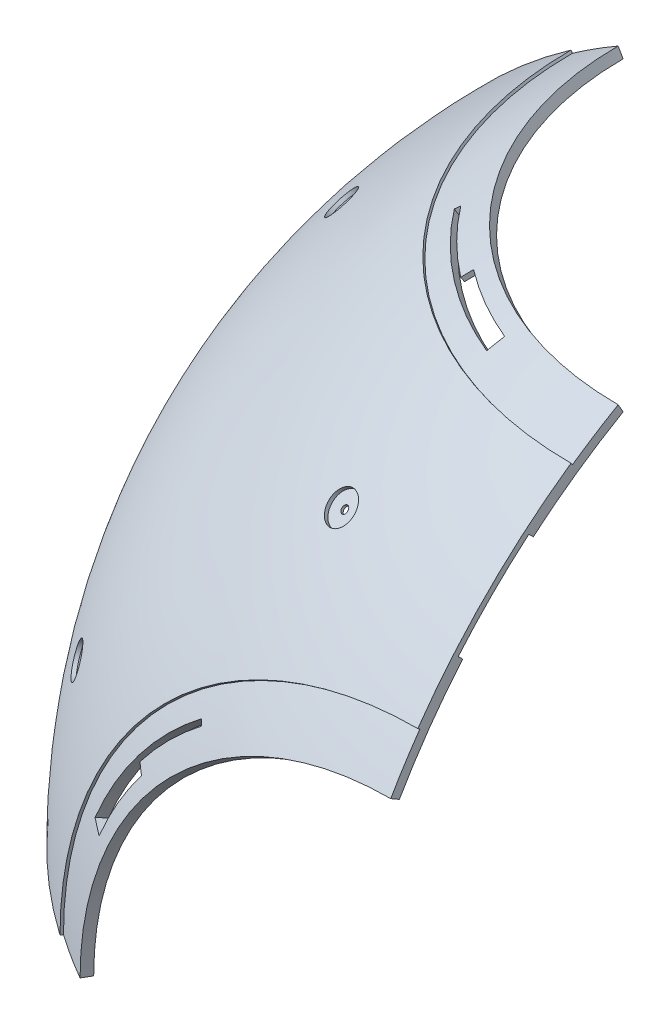
SolidWorks part; units mm, degrees
ref_plane "Front Plane" through (0, 0, 0) normal (0, 0, 1) x (1, 0, 0)
ref_plane "Top Plane" through (0, 0, 0) normal (0, 1, 0) x (1, 0, 0)
ref_plane "Right Plane" through (0, 0, 0) normal (1, 0, 0) x (0, 0, -1)
sketch "Sketch1" plane through (0, 0, 0) normal (0, 0, 1) x (1, 0, 0)
  line L0 (0, 0) -> (0, 282.4311)
  line L1 (-122.5, 212.1762) -> (-124.5, 215.6403)
  line L2 (-142.8205, 203.9689) -> (-143.3941, 204.788)
  line L3 (-245, 0) -> (-250, 0)
  arc A0 (-143.3941, 204.788) -> (-250, 0) centre (0, 0) ccw
  arc A1 (-124.5, 215.6403) -> (-142.8205, 203.9689) centre (0, 0) ccw
  arc A2 (-122.5, 212.1762) -> (-245, 0) centre (0, 0) ccw
  dimension "D1" = 500
  dimension "D2" = 498
  dimension "D3" = 490
  dimension "D4" = 5
  dimension "D5" = 30
revolve "Revolve1" add sketch "Sketch1" angle 90 about L0 region at (-214.3457, 123.7526, 0)
sketch "Sketch2" plane through (0, 0, 0) normal (1, 0, 0) x (0, 0, -1)
  line L0 (0, 0) -> (-288.7114, 0)
  line L1 (-212.1762, 122.5) -> (-215.6403, 124.5)
  line L2 (-203.9689, 142.8205) -> (-204.788, 143.3941)
  arc A0 (-204.788, 143.3941) -> (-250, 0) centre (0, 0) ccw
  arc A1 (-212.1762, 122.5) -> (-245, 0) centre (0, 0) ccw
  arc A2 (-203.9689, 142.8205) -> (-215.6403, 124.5) centre (0, 0) ccw
  dimension "D1" = 498
  dimension "D2" = 490
  dimension "D3" = 5
  dimension "D4" = 30
revolve "Cut-Revolve2" cut sketch "Sketch2" angle 360 about L0 region at (0, 1.506, 247.5)
sketch "Sketch3" plane through (0, 0, 0) normal (0, 0, -1) x (-1, 0, 0)
  line L0 (0, 0) -> (307.3195, 0)
  line L1 (203.9689, 142.8205) -> (204.788, 143.3941)
  line L2 (0, 0) -> (215.6403, 124.5)
  arc A0 (245, 0) -> (212.1762, 122.5) centre (0, 0) ccw
  arc A1 (250, 0) -> (204.788, 143.3941) centre (0, 0) ccw
  arc A2 (215.6403, 124.5) -> (203.9689, 142.8205) centre (0, 0) ccw
  dimension "D1" = 498
  dimension "D2" = 30
  dimension "D3" = 5
revolve "Cut-Revolve3" cut sketch "Sketch3" angle 360 about L0 region at (-238.1065, 63.8005, 0)
sketch "Sketch10" plane through (0, 0, 0) normal (0, 0, 1) x (1, 0, 0)
  line L0 (0, 0) -> (-235.3166, 0)
  line L1 (0, 0) -> (-214.7234, 214.7234)
  dimension "D1" = 45
ref_plane "Plane1" through (0, 0, 0) normal (0, -0.3827, 0.9239) x (-1, 0, 0)
sketch "Sketch11" plane through (0, 0, 0) normal (0, -0.3827, 0.9239) x (-1, 0, 0)
  line L0 (0, 0) -> (212.3074, -130.1021)
  line L1 (0, 0) -> (208.829, -135.6151)
  line L2 (0, 0) -> (204.788, -143.3941)
  line L3 (0, 0) -> (271.2872, 0)
  circle A0 centre (0, 0) radius 249
  circle A1 centre (0, 0) radius 245
  dimension "D1" = 498
  dimension "D2" = 490
  dimension "D3" = 1.5
  dimension "D4" = 2
revolve "Cut-Revolve4" cut sketch "Sketch11" angle 15 about L0 region at (-208.8934, 121.7691, 50.4384) reverse direction yes
sketch "Sketch12" plane through (0, 0, 0) normal (0, 0.6088, -0.7934) x (1, 0, 0)
  line L0 (0, 0) -> (-210.0045, -133.7876)
  line L1 (0, 0) -> (-208.829, -135.6151)
  line L2 (0, 0) -> (-204.788, -143.3941)
  line L3 (0, 0) -> (-212.3074, -130.1021)
  circle A0 centre (0, 0) radius 249
  circle A1 centre (0, 0) radius 245
  circle A2 centre (0, 0) radius 247
  dimension "D1" = 490
  dimension "D4" = 494
  dimension "D2" = 2
  dimension "D3" = 0.5
revolve "Cut-Revolve5" cut sketch "Sketch12" angle 15 about L0 region at (-206.8961, 105.5795, 81.014) region at (-208.6183, 103.4209, 79.3577) region at (-208.5781, 106.4378, 81.6726) reverse direction yes
ref_plane "Plane2" through (0, 0, 0) normal (0, -0.7071, 0.7071) x (-1, 0, 0)
sketch "Sketch15" plane through (0, 0, 0) normal (0, 1, 0) x (1, 0, 0)
  line L1 (0, 0) -> (-189.3752, -189.3752)
  line L2 (0, 0) -> (0, -178.2847)
  dimension "D1" = 45
ref_plane "Plane3" through (0, 0, 0) normal (-0.7071, 0, -0.7071) x (-0.7071, 0, 0.7071)
ref_axis "Axis1" through (9.4688, -9.4688, -9.4688) along (-0.5774, 0.5774, 0.5774)
pattern_circular "CirPattern5" count 3 every 120 about axis through (9.4688, -9.4688, -9.4688) along (-0.5774, 0.5774, 0.5774) of "Cut-Revolve4", "Cut-Revolve5"
sketch "Sketch18" plane through (0, 0, 0) normal (-0.7071, 0, -0.7071) x (-0.7071, 0, 0.7071)
  line L0 (0, 0) -> (0, 83.9389)
ref_plane "Plane5" through (0, 0, 0) normal (-0.7071, 0, 0.7071) x (0, 1, 0)
sketch "Sketch19" plane through (0, 0, 0) normal (-0.7071, 0, 0.7071) x (0, 1, 0)
  line L0 (0, 64.4459) -> (0, -64.4459)
sketch "Sketch20" plane through (0, 0, 0) normal (0, -1, 0) x (1, 0, 0)
  line L0 (0, 0) -> (-202.4375, 202.4375)
  line L1 (14.1421, 14.1421) -> (-188.2954, 216.5796)
  line L2 (-14.1421, -14.1421) -> (-216.5796, 188.2954)
  circle A0 centre (0, 0) radius 247.5
  circle A1 centre (0, 0) radius 245
  dimension "D3" = 495
  dimension "D1" = 20
  dimension "D2" = 20
revolve "Cut-Revolve6" cut sketch "Sketch20" angle 20 about L0 region at (-181.0082, 0, 166.8583) region at (-166.8583, 0, 181.0082) reverse direction yes
pattern_circular "CirPattern6" count 3 over 360 about axis through (9.4688, -9.4688, -9.4688) along (-0.5774, 0.5774, 0.5774) of "Cut-Revolve6"
ref_plane "Plane6" through (0, 0, 0) normal (0.183, 0.9659, -0.183) x (0.7071, 0, 0.7071)
sketch "Sketch21" plane through (0, 0, 0) normal (0.183, 0.9659, -0.183) x (0.7071, 0, 0.7071)
  line L0 (0, 0) -> (0, -320.9384)
sketch "Sketch22" plane through (0, 0, 0) normal (-0.7071, 0, -0.7071) x (-0.7071, 0, 0.7071)
  line L0 (0, 0) -> (310.0027, 83.065) construction
  line L1 (0, 0) -> (310.0027, 83.065)
  line L2 (0.3882, -1.4489) -> (310.391, 81.6161)
  line L3 (1.6823, -6.2785) -> (311.6851, 76.7865)
  circle A0 centre (0, 0) radius 250
  circle A1 centre (0, 0) radius 248.5
  circle A2 centre (0, 0) radius 299.5165
  circle A3 centre (0, 0) radius 234.5409
  dimension "D1" = 497
  dimension "D2" = 500
  dimension "D3" = 1.5
  dimension "D4" = 5
revolve "Cut-Revolve13" cut sketch "Sketch22" angle 360 about L1 region at (-165.0977, 61.7852, 165.0977) region at (-170.3771, 63.7858, 170.3771) region at (-170.9482, 60.6374, 170.9482)
pattern_circular "CirPattern8" count 3 every 120 about axis through (9.4688, -9.4688, -9.4688) along (-0.5774, 0.5774, 0.5774) of "Cut-Revolve13"
